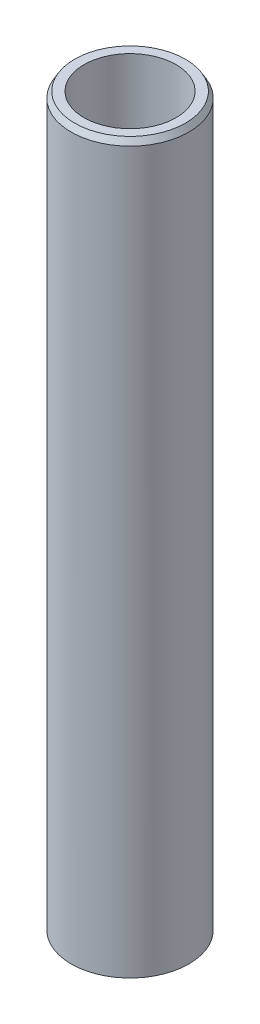
SolidWorks part; units mm, degrees
ref_plane "Front Plane" through (0, 0, 0) normal (0, 0, 1) x (1, 0, 0)
ref_plane "Top Plane" through (0, 0, 0) normal (0, 1, 0) x (1, 0, 0)
ref_plane "Right Plane" through (0, 0, 0) normal (1, 0, 0) x (0, 0, -1)
sketch "Sketch1" plane through (0, 0, 0) normal (0, 1, 0) x (1, 0, 0)
  circle A0 centre (0, 0) radius 40
  dimension "SHAFT_OD" = 80
extrude "Boss-Extrude1" add sketch "Sketch1" along normal blind 495.8579
sketch "Sketch2" plane through (0, 0, 0) normal (0, 1, 0) x (1, 0, 0)
  circle A0 centre (0, 0) radius 31.2654
  dimension "BORE_D" = 62.5308
extrude "Cut-Extrude1" cut sketch "Sketch2" along normal through all
chamfer "Chamfer1" distance 4.0839 angle 30 2 edges at (0, 495.8579, 40) (0, 0, 40) first distance on face at (0, 495.8579, 40) first distance on face at (0, 0, 31.2654)
